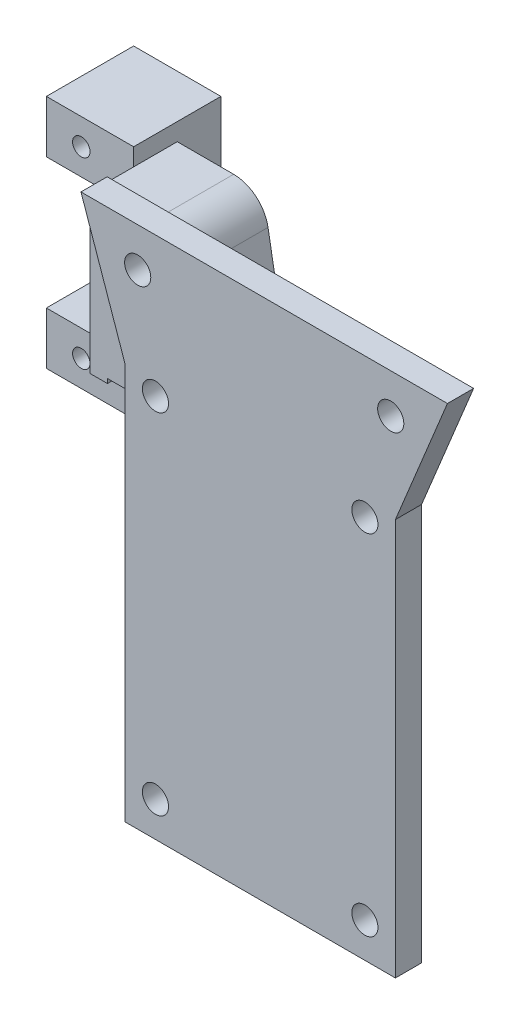
SolidWorks part; units mm, degrees
ref_plane "Front Plane" through (0, 0, 0) normal (0, 0, 1) x (1, 0, 0)
ref_plane "Top Plane" through (0, 0, 0) normal (0, 1, 0) x (1, 0, 0)
ref_plane "Right Plane" through (0, 0, 0) normal (1, 0, 0) x (0, 0, -1)
sketch "Sketch1" plane through (0, 0, 0) normal (0, 0, 1) x (1, 0, 0)
  line L1 (0, 0) -> (31, 0)
  line L2 (0, 0) -> (0, 45.5)
  line L3 (-5.037, 60) -> (36.963, 60)
  line L4 (31, 0) -> (31, 45.5)
  line L5 (36.963, 60) -> (31, 45.5)
  line L7 (-5.037, 60) -> (0, 45.5)
  circle A0 centre (30.463, 55.5) radius 1.5
  circle A1 centre (27.5, 44) radius 1.5
  circle A4 centre (27.5, 4) radius 1.5
  circle A5 centre (3.5, 4) radius 1.5
  circle A7 centre (3.5, 44) radius 1.5
  circle A9 centre (1.463, 55.5) radius 1.5
  point P1 (31, 50.4189)
  point P2 (0, 0)
  point P13 (0, 46.012)
  point P14 (0, 0)
  point P15 (31, 45.5)
  point P29 (15.963, 60)
  dimension "D4" = 3
  dimension "D5" = 21
  dimension "D6" = 2
  dimension "D7" = 2
  dimension "D8" = 21
  dimension "D9" = 2.5
  dimension "D10" = 37
  dimension "D11" = 2.8
  dimension "D12" = 29
  dimension "D13" = 14.5
  dimension "D14" = 11.5
  dimension "D15" = 3
  dimension "D16" = 5
  dimension "D2" = 0
  dimension "D3" = 31
extrude "Boss-Extrude1" add sketch "Sketch1" along normal blind 3
sketch "Sketch3" plane through (0, 0, 0) normal (0, 0, -1) x (-1, 0, 0)
  line L0 (-5.4017, 56.1977) -> (-7.4387, 44.6977)
  line L2 (5, 40) -> (-3.5, 40)
  line L3 (-1.463, 59.5) -> (5, 59.5)
  line L4 (5, 59.5) -> (5, 40)
  line L6 (0, 0) -> (0, 45.5)
  line L7 (0, 45.5) -> (5.037, 60)
  line L8 (5.037, 60) -> (-36.963, 60)
  line L9 (-36.963, 60) -> (-31, 45.5)
  line L10 (-31, 45.5) -> (-31, 0)
  line L11 (-31, 0) -> (0, 0)
  line L12 (0, 0) -> (0, 45.5) construction
  circle A0 centre (-1.463, 55.5) radius 1.5 construction
  circle A1 centre (-1.463, 55.5) radius 1.5 construction
  circle A2 centre (-1.463, 55.5) radius 2.5
  arc A3 (-1.463, 59.5) -> (-5.4017, 56.1977) centre (-1.463, 55.5) ccw
  circle A4 centre (-3.5, 44) radius 1.5 construction
  circle A5 centre (-3.5, 44) radius 1.5
  arc A6 (-7.4387, 44.6977) -> (-3.5, 40) centre (-3.5, 44) ccw
  dimension "D2" = 5
  dimension "D3" = 8
  dimension "D4" = 8
  dimension "D5" = 5
  dimension "D1" = 0
extrude "Boss-Extrude2" add sketch "Sketch3" along normal blind 5 separate body
sketch "Sketch6" plane through (0, 0, -5) normal (0, 0, -1) x (-1, 0, 0)
  line L8 (-5.4017, 56.1977) -> (-7.4387, 44.6977)
  line L9 (-3.5, 40) -> (5, 40)
  line L10 (5, 40) -> (5, 59.5)
  line L11 (5, 59.5) -> (-1.463, 59.5)
  line L12 (-5.4017, 56.1977) -> (-6.2303, 51.5197)
  line L13 (3.4282, 40) -> (5, 40)
  line L14 (5, 40) -> (5, 59.5)
  line L15 (5, 59.5) -> (-1.463, 59.5)
  arc A0 (0.459, 43.4286) -> (-3.3722, 47.998) centre (-3.5, 44) ccw
  arc A1 (-6.2303, 51.5197) -> (-3.3722, 47.998) centre (-3.2763, 50.9964) ccw
  arc A2 (-1.463, 59.5) -> (-5.4017, 56.1977) centre (-1.463, 55.5) ccw
  arc A3 (-7.4387, 44.6977) -> (-3.5, 40) centre (-3.5, 44) ccw
  arc A4 (-1.463, 59.5) -> (-5.4017, 56.1977) centre (-1.463, 55.5) ccw
  arc A6 (3.4282, 40) -> (0.459, 43.4286) centre (3.4282, 43) cw
  circle A7 centre (-1.463, 55.5) radius 2.5 construction
  circle A8 centre (-1.463, 55.5) radius 2.5
  dimension "D2" = 3
  dimension "D1" = 0
extrude "Boss-Extrude5" add sketch "Sketch6" along normal blind 3
sketch "Sketch8" plane through (0, 0, -5) normal (0, 0, -1) x (-1, 0, 0)
  line L1 (-3.5, 41) -> (-0.9019, 42.5)
  line L6 (-0.9019, 42.5) -> (-0.9019, 45.5)
  line L7 (-0.9019, 45.5) -> (-3.5, 47)
  line L8 (-3.5, 47) -> (-6.0981, 45.5)
  line L9 (-6.0981, 45.5) -> (-6.0981, 42.5)
  line L10 (-6.0981, 42.5) -> (-3.5, 41)
  circle A0 centre (-3.5, 44) radius 2.5981 construction
  point P0 (0, 0)
  dimension "D2" = 6
extrude "Cut-Extrude1" cut sketch "Sketch8" against normal blind 3
sketch "Sketch4" plane through (-5, 0, 0) normal (-1, 0, 0) x (0, 0, 1)
  line L0 (0, 61.5) -> (0, 34.5)
  line L1 (0, 34.5) -> (-13, 34.5)
  line L2 (-13, 34.5) -> (-13, 61.5)
  line L3 (-13, 61.5) -> (0, 61.5)
  line L5 (0, 55.5) -> (-4, 55.5) construction
  line L6 (-8, 59.5) -> (0, 59.5) construction
  line L7 (0, 40) -> (0, 59.5) construction
  dimension "D1" = 27
  dimension "D2" = 4
  dimension "D3" = 4
  dimension "D4" = 6
  dimension "D5" = 13
extrude "Boss-Extrude7" add sketch "Sketch4" along normal blind 2
sketch "Sketch9" plane through (-7, 0, 0) normal (-1, 0, 0) x (0, 0, 1)
  line L1 (-13, 61.5) -> (-3, 61.5)
  line L2 (-13, 61.5) -> (-13, 55.5)
  line L3 (-13, 55.5) -> (-3, 55.5)
  line L4 (-3, 61.5) -> (-3, 55.5)
  line L5 (-13, 34.5) -> (-3, 34.5)
  line L6 (-13, 34.5) -> (-13, 40.5)
  line L7 (-13, 40.5) -> (-3, 40.5)
  line L8 (-3, 34.5) -> (-3, 40.5)
  line L9 (0, 34.5) -> (0, 61.5) construction
  dimension "D1" = 6
  dimension "D2" = 3
  dimension "D3" = 3
  dimension "D4" = 6
extrude "Boss-Extrude8" add sketch "Sketch9" along normal blind 8
sketch "Sketch10" plane through (-7, 0, 0) normal (-1, 0, 0) x (0, 0, 1)
  line L0 (0, -28.5797) -> (0, 28.5797) construction
  line L1 (-3, 56.5) -> (0, 56.5)
  line L2 (-3, 56.5) -> (-3, 61.5)
  line L3 (-3, 61.5) -> (0, 61.5)
  line L4 (0, 56.5) -> (0, 61.5)
  line L5 (0, 61.5) -> (-3, 61.5) construction
  line L6 (-3, 34.5) -> (0, 34.5) construction
  line L7 (-3, 39.5) -> (0, 39.5)
  line L8 (-3, 39.5) -> (-3, 34.5)
  line L9 (-3, 34.5) -> (0, 34.5)
  line L10 (0, 39.5) -> (0, 34.5)
  line L11 (-3, 34.5) -> (-3, 40.5) construction
  line L12 (-3, 55.5) -> (-3, 61.5) construction
  point P16 (0, 0)
  point P17 (0, 0)
  dimension "D1" = 5
  dimension "D2" = 5
extrude "Cut-Extrude2" cut sketch "Sketch10" against normal blind 2
sketch "Sketch11" plane through (0, 0, -3) normal (0, 0, 1) x (1, 0, 0)
  line L0 (-15, 34.5) -> (-15, 40.5) construction
  line L2 (-15, 34.5) -> (-5, 34.5) construction
  line L3 (-15, 61.5) -> (-5, 61.5) construction
  line L4 (-15, 55.5) -> (-15, 61.5) construction
  circle A0 centre (-11, 37.5) radius 1
  circle A1 centre (-11, 58.5) radius 1
  dimension "D3" = 2
  dimension "D4" = 2
  dimension "D1" = 4
  dimension "D2" = 3
  dimension "D5" = 3
  dimension "D6" = 4
extrude "Cut-Extrude3" cut sketch "Sketch11" against normal up to next (10 mm away)
